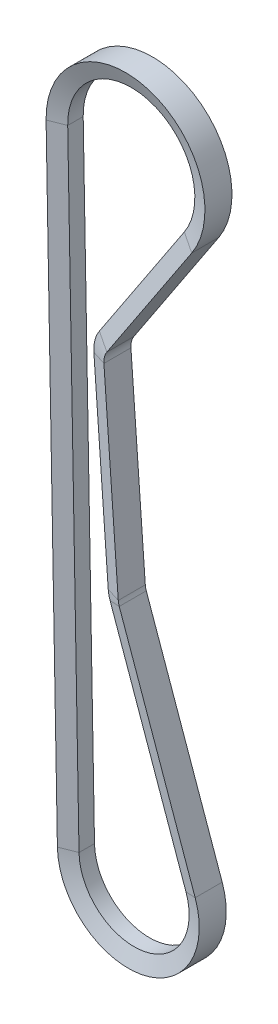
SolidWorks part; units mm, degrees
ref_plane "Front Plane" through (0, 0, 0) normal (0, 0, 1) x (1, 0, 0)
ref_plane "Top Plane" through (0, 0, 0) normal (0, 1, 0) x (1, 0, 0)
ref_plane "Right Plane" through (0, 0, 0) normal (1, 0, 0) x (0, 0, -1)
sketch "Sketch2" plane through (0, 0, 0) normal (0, 0, 1) x (1, 0, 0)
  line L0 (0, 0) -> (1, 0) construction
  line L1 (0, 0) -> (0, 1) construction
  line L12 (-24.9959, -0.4531) -> (-28.9832, 219.4903)
  line L14 (22.3604, 204.5427) -> (-7.5641, 159.3354)
  line L15 (-8.6024, 155.3714) -> (-3.543, 85.5545)
  line L16 (-3.1952, 83.8932) -> (23.5652, 8.3475)
  arc A4 (-28.9832, 219.4903) -> (22.3604, 204.5427) centre (-0.9878, 219.9978) cw
  arc A7 (23.5652, 8.3475) -> (-24.9959, -0.4531) centre (0, 0) cw
  arc A8 (-7.5641, 159.3354) -> (-8.6024, 155.3714) centre (-2.2691, 155.8304) ccw
  arc A9 (-3.543, 85.5545) -> (-3.1952, 83.8932) centre (2.7904, 86.0135) ccw
ref_plane "Plane4" through (23.5652, 8.3475, 0) normal (0.3339, -0.9426, 0) x (-0.9426, -0.3339, 0)
sketch "Sketch3" plane through (23.5652, 8.3475, 0) normal (0.3339, -0.9426, 0) x (-0.9426, -0.3339, 0)
  line L0 (0, -4.7625) -> (0, 4.7625)
  line L1 (0, -4.7625) -> (5.588, -2.7286)
  line L2 (5.588, -2.7286) -> (5.588, 2.7286)
  line L3 (5.588, 2.7286) -> (0, 4.7625)
  line L4 (0, 0) -> (5.588, 0) construction
  dimension "D1" = 9.525
  dimension "D2" = 5.588
  dimension "D3" = 40
sweep "Sweep1" add profiles "Sketch3" path "Sketch2"
